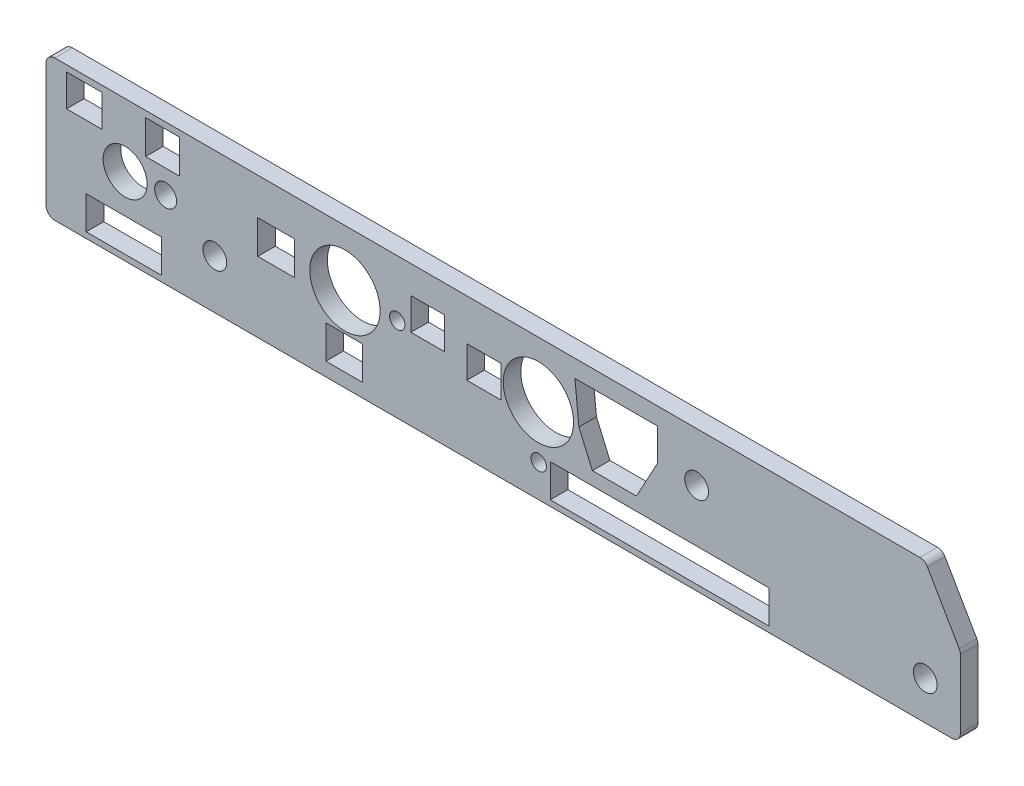
SolidWorks part; units mm, degrees
material "Acrylic (Medium-high impact)"
ref_plane "Front Plane" through (0, 0, 0) normal (0, 0, 1) x (1, 0, 0)
ref_plane "Top Plane" through (0, 0, 0) normal (0, 1, 0) x (1, 0, 0)
ref_plane "Right Plane" through (0, 0, 0) normal (1, 0, 0) x (0, 0, -1)
sketch "Sketch1" plane through (0, 0, 0) normal (0, 0, 1) x (1, 0, 0)
  line L5 (157.7677, 0) -> (1.5875, 0)
  line L6 (0, -1.5875) -> (0, -23.8125)
  line L7 (1.5875, -25.4) -> (163.5125, -25.4)
  line L8 (165.1, -23.8125) -> (165.1, -11.5379)
  line L9 (164.8873, -10.7441) -> (159.1425, -0.7937)
  line L10 (157.7677, 0) -> (1.5875, 0)
  line L11 (0, -1.5875) -> (0, -23.8125)
  line L12 (1.5875, -25.4) -> (163.5125, -25.4)
  line L13 (165.1, -23.8125) -> (165.1, -11.5379)
  line L14 (164.8873, -10.7441) -> (159.1425, -0.7937)
  arc A5 (159.1425, -0.7937) -> (157.7677, 0) centre (157.7677, -1.5875) ccw
  arc A6 (1.5875, 0) -> (0, -1.5875) centre (1.5875, -1.5875) ccw
  arc A7 (0, -23.8125) -> (1.5875, -25.4) centre (1.5875, -23.8125) ccw
  arc A8 (163.5125, -25.4) -> (165.1, -23.8125) centre (163.5125, -23.8125) ccw
  arc A9 (165.1, -11.5379) -> (164.8873, -10.7441) centre (163.5125, -11.5379) ccw
  arc A10 (159.1425, -0.7937) -> (157.7677, 0) centre (157.7677, -1.5875) ccw
  arc A11 (1.5875, 0) -> (0, -1.5875) centre (1.5875, -1.5875) ccw
  arc A12 (0, -23.8125) -> (1.5875, -25.4) centre (1.5875, -23.8125) ccw
  arc A13 (163.5125, -25.4) -> (165.1, -23.8125) centre (163.5125, -23.8125) ccw
  arc A14 (165.1, -11.5379) -> (164.8873, -10.7441) centre (163.5125, -11.5379) ccw
  dimension "D1" = 0
extrude "Boss-Extrude1" add sketch "Sketch1" along normal blind 3.175
hole_wizard "1/2 (0.5) Diameter Hole1" positions "Sketch3" profile "Sketch2" hole size "1/2" standard "ANSI Inch" end condition through all
sketch "Sketch3" plane through (0, 0, 0) normal (0, 0, -1) x (-1, 0, 0)
  point P0 (-53.975, -10.16)
  point P3 (-88.9, -10.16)
sketch "Sketch2" plane through (53.975, -10.16, 0) normal (1, 0, 0) x (0, 1, 0)
  line L0 (0, 0) -> (0, 3.175)
  line L1 (0, 3.175) -> (6.35, 3.175)
  line L2 (6.35, 3.175) -> (6.35, 0)
  line L5 (6.35, 0) -> (0, 0)
  line L11 (0, -6.35) -> (0, 107.95) construction
  dimension "Thru Hole Dia." = 12.7
  dimension "Thru Hole Depth" = 3.175
hole_wizard "5/16 (0.3125) Diameter Hole1" positions "Sketch5" profile "Sketch4" hole size "5/16" standard "ANSI Inch" end condition through all
sketch "Sketch5" plane through (0, 0, 0) normal (0, 0, -1) x (-1, 0, 0)
  point P0 (-14.2875, -11.43)
sketch "Sketch4" plane through (14.2875, -11.43, 0) normal (1, 0, 0) x (0, 1, 0)
  line L0 (0, 0) -> (0, 3.175)
  line L1 (0, 3.175) -> (3.9688, 3.175)
  line L2 (3.9688, 3.175) -> (3.9688, 0)
  line L5 (3.9688, 0) -> (0, 0)
  line L11 (0, -6.35) -> (0, 107.95) construction
  dimension "Thru Hole Dia." = 7.9375
  dimension "Thru Hole Depth" = 3.175
hole_wizard "5/32 (0.15625) Diameter Hole1" positions "Sketch7" profile "Sketch6" hole size "5/32" standard "ANSI Inch" end condition through all
sketch "Sketch7" plane through (0, 0, 0) normal (0, 0, -1) x (-1, 0, 0)
  point P0 (-21.5983, -11.43)
sketch "Sketch6" plane through (21.5983, -11.43, 0) normal (1, 0, 0) x (0, 1, 0)
  line L0 (0, 0) -> (0, 3.175)
  line L1 (0, 3.175) -> (1.9844, 3.175)
  line L2 (1.9844, 3.175) -> (1.9844, 0)
  line L5 (1.9844, 0) -> (0, 0)
  line L11 (0, -6.35) -> (0, 107.95) construction
  dimension "Thru Hole Dia." = 3.9688
  dimension "Thru Hole Depth" = 3.175
hole_wizard "7/64 (0.10938) Diameter Hole1" positions "Sketch9" profile "Sketch8" hole size "7/64" standard "ANSI Inch" end condition through all
sketch "Sketch9" plane through (0, 0, 0) normal (0, 0, -1) x (-1, 0, 0)
  point P0 (-88.9595, -19.5375)
  point P2 (-63.4234, -10.16)
sketch "Sketch8" plane through (88.9595, -19.5375, 0) normal (1, 0, 0) x (0, 1, 0)
  line L0 (0, 0) -> (0, 3.175)
  line L1 (0, 3.175) -> (1.3891, 3.175)
  line L2 (1.3891, 3.175) -> (1.3891, 0)
  line L5 (1.3891, 0) -> (0, 0)
  line L11 (0, -6.35) -> (0, 107.95) construction
  dimension "Thru Hole Dia." = 2.7783
  dimension "Thru Hole Depth" = 3.175
hole_wizard "#6 Clearance Hole1" positions "Sketch11" profile "Sketch10" hole size "#6" standard "ANSI Inch" end condition through all
sketch "Sketch11" plane through (0, 0, 0) normal (0, 0, -1) x (-1, 0, 0)
  point P0 (-158.75, -18.415)
  point P3 (-117.475, -8.89)
  point P6 (-30.48, -16.51)
sketch "Sketch10" plane through (158.75, -18.415, 0) normal (1, 0, 0) x (0, 1, 0)
  line L0 (0, 0) -> (0, 3.175)
  line L1 (0, 3.175) -> (2.1526, 3.175)
  line L2 (2.1526, 3.175) -> (2.1526, 0)
  line L5 (2.1526, 0) -> (0, 0)
  line L11 (0, -6.35) -> (0, 107.95) construction
  dimension "Thru Hole Dia." = 4.3053
  dimension "Thru Hole Depth" = 3.175
sketch "Sketch12" plane through (0, 0, 0) normal (0, 0, -1) x (-1, 0, 0)
  line L0 (-98.6504, -15.9904) -> (-106.6203, -15.9904)
  line L1 (-106.6203, -15.9904) -> (-110.3674, -9.0316)
  line L2 (-110.3674, -9.0316) -> (-110.3674, -3.1434)
  line L3 (-110.3674, -3.1434) -> (-95.4981, -3.1434)
  line L4 (-95.4981, -3.1434) -> (-96.214, -10.387)
  line L5 (-96.214, -10.387) -> (-98.6504, -15.9904)
  line L7 (-7.2591, -24.3536) -> (-20.8879, -24.3536)
  line L8 (-7.2591, -24.3536) -> (-7.2591, -18.3859)
  line L9 (-7.2591, -18.3859) -> (-20.8879, -18.3859)
  line L10 (-20.8879, -24.3536) -> (-20.8879, -18.3859)
  line L11 (-3.7107, -6.8941) -> (-10.122, -6.8941)
  line L12 (-3.7107, -6.8941) -> (-3.7107, -1.1281)
  line L13 (-3.7107, -1.1281) -> (-10.122, -1.1281)
  line L14 (-10.122, -6.8941) -> (-10.122, -1.1281)
  line L15 (-17.9847, -7.2167) -> (-24.1137, -7.2167)
  line L16 (-17.9847, -7.2167) -> (-17.9847, -1.1281)
  line L17 (-17.9847, -1.1281) -> (-24.1137, -1.1281)
  line L18 (-24.1137, -7.2167) -> (-24.1137, -1.1281)
  line L19 (-38.2264, -12.7005) -> (-44.8392, -12.7005)
  line L20 (-38.2264, -12.7005) -> (-38.2264, -6.6522)
  line L21 (-38.2264, -6.6522) -> (-44.8392, -6.6522)
  line L22 (-44.8392, -12.7005) -> (-44.8392, -6.6522)
  line L23 (-50.5246, -22.9423) -> (-57.1374, -22.9423)
  line L24 (-50.5246, -22.9423) -> (-50.5246, -16.9343)
  line L25 (-50.5246, -16.9343) -> (-57.1374, -16.9343)
  line L26 (-57.1374, -22.9423) -> (-57.1374, -16.9343)
  line L27 (-65.8797, -10.7482) -> (-71.9164, -10.7482)
  line L28 (-65.8797, -10.7482) -> (-65.8797, -5.0076)
  line L29 (-65.8797, -5.0076) -> (-71.9164, -5.0076)
  line L30 (-71.9164, -10.7482) -> (-71.9164, -5.0076)
  line L31 (-75.9713, -13.2084) -> (-82.1219, -13.2084)
  line L32 (-75.9713, -13.2084) -> (-75.9713, -7.4679)
  line L33 (-75.9713, -7.4679) -> (-82.1219, -7.4679)
  line L34 (-82.1219, -13.2084) -> (-82.1219, -7.4679)
  line L35 (-91.0517, -24.3536) -> (-130.5395, -24.3536)
  line L36 (-91.0517, -24.3536) -> (-91.0517, -18.3859)
  line L37 (-91.0517, -18.3859) -> (-130.5395, -18.3859)
  line L38 (-130.5395, -24.3536) -> (-130.5395, -18.3859)
extrude "Cut-Extrude1" cut sketch "Sketch12" against normal through all
